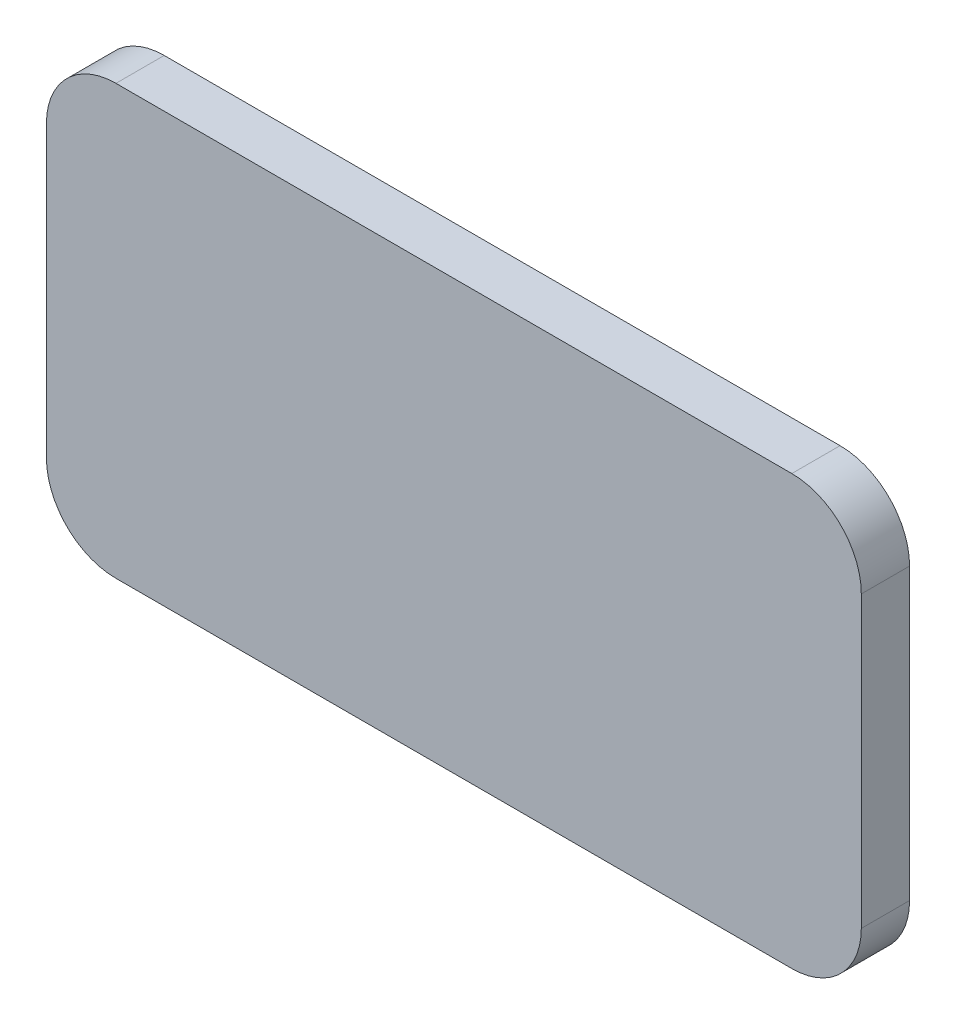
SolidWorks part; units mm, degrees
ref_plane "Спереди" through (0, 0, 0) normal (0, 0, 1) x (1, 0, 0)
ref_plane "Сверху" through (0, 0, 0) normal (0, 1, 0) x (1, 0, 0)
ref_plane "Справа" through (0, 0, 0) normal (1, 0, 0) x (0, 0, -1)
sketch "Эскиз1" plane through (0, 0, 0) normal (0, 0, 1) x (1, 0, 0)
  line L24 (42.2, -15) -> (42.2, 15)
  line L25 (35, 15) -> (-35, 15) construction
  line L26 (35, 15) -> (35, -15) construction
  line L27 (35, -15) -> (-35, -15) construction
  line L28 (-35, 15) -> (-35, -15) construction
  line L29 (35, 15) -> (-35, -15) construction
  line L30 (35, -15) -> (-35, 15) construction
  line L31 (35, 22.2) -> (-35, 22.2)
  line L32 (-42.2, 15) -> (-42.2, -15)
  line L33 (-35, -22.2) -> (35, -22.2)
  arc A0 (42.2, -15) -> (35, -22.2) centre (35, -15) cw
  arc A2 (-35, -22.2) -> (-42.2, -15) centre (-35, -15) cw
  arc A3 (-42.2, 15) -> (-35, 22.2) centre (-35, 15) cw
  arc A4 (42.2, 15) -> (35, 22.2) centre (35, 15) ccw
  point P0 (0, 0)
  dimension "D3" = 7.2
  dimension "D1" = 30
  dimension "D2" = 70
extrude "Бобышка-Вытянуть1" add sketch "Эскиз1" along normal blind 5
